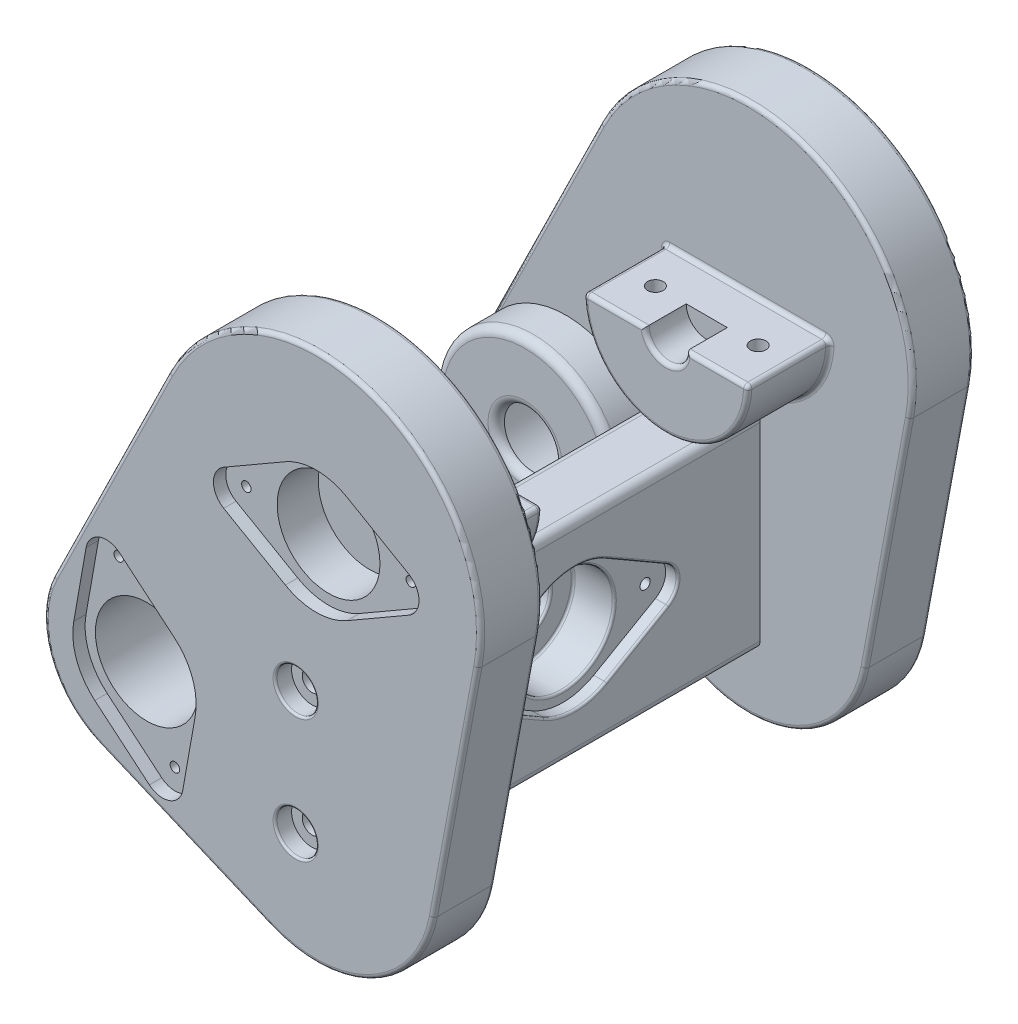
SolidWorks part; units mm, degrees
other "Markup1"
sketch "Sketch17" plane through (40, 40, -60) normal (0.6706, 0.1026, -0.7347) x (-0.7381, -0.0065, -0.6746)
ref_plane "Front Plane" through (0, 0, 0) normal (0, 0, 1) x (1, 0, 0)
ref_plane "Top Plane" through (0, 0, 0) normal (0, 1, 0) x (1, 0, 0)
ref_plane "Right Plane" through (0, 0, 0) normal (1, 0, 0) x (0, 0, -1)
ref_plane "Plane1" through (0, 0, 60) normal (0, 0, 1) x (1, 0, 0)
sketch "Sketch2" plane through (0, 0, 60) normal (0, 0, 1) x (1, 0, 0)
  line L2 (0, -60) -> (0, 0) construction
  line L3 (-39.322, -7.3333) -> (-28.5085, -65.3167)
  line L4 (39.322, -7.3333) -> (28.5085, -65.3167)
  circle A0 centre (0, 0) radius 30 construction
  arc A1 (39.322, -7.3333) -> (-39.322, -7.3333) centre (0, 0) ccw
  circle A2 centre (0, -60) radius 24 construction
  arc A3 (-28.5085, -65.3167) -> (28.5085, -65.3167) centre (0, -60) ccw
  circle A4 centre (0, 0) radius 12.5
  circle A5 centre (0, -60) radius 12.5 construction
  dimension "D1" = 60
  dimension "D2" = 10
  dimension "D5" = 48
  dimension "D6" = 5
  dimension "D7" = 25
  dimension "D8" = 25
  dimension "D3" = 60
extrude "Boss-Extrude1" add sketch "Sketch2" against normal blind 15
sketch "Sketch13" plane through (0, 0, 45) normal (0, 0, -1) x (-1, 0, 0)
  line L0 (0, 0) -> (0, -60) construction
  line L2 (13, -74) -> (-3, -74)
  line L3 (13, -74) -> (13, -24)
  line L4 (13, -24) -> (-3, -24)
  line L5 (-3, -74) -> (-3, -24)
  line L6 (13, -74) -> (-3, -24) construction
  line L7 (13, -24) -> (-3, -74) construction
  point P9 (5, -49)
  dimension "D1" = 16
  dimension "D2" = 50
  dimension "D3" = 11
  dimension "D4" = 5
extrude "Boss-Extrude5" add sketch "Sketch13" along normal up to surface (45 mm away) up to plane "Front Plane"
mirror "Mirror2" about plane through (0, 0, 0) normal (0, 0, 1) of "Boss-Extrude1", "Boss-Extrude5"
mirror "Mirror4" about plane through (0, 0, 0) normal (0, 0, 1) of "Boss-Extrude1"
sketch "Sketch5" plane through (0, 0, 0) normal (0, 0, 1) x (1, 0, 0)
  point P0 (0, 0)
sketch "Sketch14" plane through (3, 0, 0) normal (1, 0, 0) x (0, 0, -1)
  line L0 (45, -24) -> (-45, -24) construction
  circle A0 centre (0, -49) radius 12.5
  dimension "D1" = 25
  dimension "D2" = 25
extrude "Cut-Extrude1" cut sketch "Sketch14" against normal blind 13
sketch "Sketch15" plane through (3, 0, 0) normal (1, 0, 0) x (0, 0, -1)
  line L0 (-22.5, -44.6699) -> (-7.5, -36.0096)
  line L1 (7.5, -36.0096) -> (22.5, -44.6699)
  line L2 (-22.5, -53.3301) -> (-7.5, -61.9904)
  line L3 (7.5, -61.9904) -> (22.5, -53.3301)
  arc A0 (-7.5, -61.9904) -> (7.5, -61.9904) centre (0, -49) ccw
  circle A1 centre (20, -49) radius 1.25
  circle A2 centre (-20, -49) radius 1.25
  arc A3 (-22.5, -44.6699) -> (-22.5, -53.3301) centre (-20, -49) ccw
  arc A4 (22.5, -53.3301) -> (22.5, -44.6699) centre (20, -49) ccw
  arc A5 (7.5, -36.0096) -> (-7.5, -36.0096) centre (0, -49) ccw
  dimension "D1" = 30
  dimension "D2" = 2.5
  dimension "D3" = 20
  dimension "D4" = 20
extrude "Cut-Extrude2" cut sketch "Sketch15" against normal blind 3
sketch "Sketch16" plane through (3, 0, 0) normal (1, 0, 0) x (0, 0, -1)
  circle A0 centre (0, -49) radius 7
  circle A5 centre (20, -49) radius 1.25 construction
  circle A6 centre (-20, -49) radius 1.25 construction
  circle A7 centre (20, -49) radius 1.25
  circle A8 centre (-20, -49) radius 1.25
  dimension "D3" = 14
extrude "Cut-Extrude3" cut sketch "Sketch16" against normal through all
fillet "Fillet3" radius 0.5 3 edges at (-10, -49, -7) (0, -49, -12.5) (-10, -49, -12.5)
fillet "Fillet4" radius 0.5 1 edges at (-13, -49, -7)
fillet "Fillet5" radius 0.5 8 edges at (3, -34, 0) (3, -40.3397, -15) (3, -49, -25) (3, -57.6603, -15) (3, -64, 0) (3, -57.6603, 15) (3, -49, 25) (3, -40.3397, 15)
sketch "Sketch18" plane through (0, 0, 0) normal (0, 0, 1) x (1, 0, 0)
  line L0 (0, 0) -> (0, -49) construction
  line L1 (0, -49) -> (60, -49) construction
  line L2 (60, -49) -> (0, 0) construction
  dimension "D1" = 49
  dimension "D2" = 60
sketch "Sketch21" plane through (0, 0, 45) normal (0, 0, -1) x (-1, 0, 0)
  line L0 (0, 0) -> (0, -49) construction
  line L1 (0, -49) -> (-44.2154, -49) construction
  line L2 (-44.2154, -49) -> (0, 0) construction
  line L5 (-63.9491, -39.2748) -> (-35.8795, 17.6822)
  line L6 (-52.7436, -69.2798) -> (-11.2417, -86.7324)
  line L7 (-39.322, -7.3333) -> (-28.5085, -65.3167)
  line L8 (39.322, -7.3333) -> (32.1833, -45.612)
  line L9 (52.7436, -69.2798) -> (11.2417, -86.7324)
  line L10 (63.9491, -39.2748) -> (35.8795, 17.6822)
  line L11 (31.7709, -47.8233) -> (28.5085, -65.3167)
  line L12 (35.8795, 17.6822) -> (11.2417, -86.7324)
  circle A0 centre (0, 0) radius 44 construction
  arc A1 (-63.9491, -39.2748) -> (-52.7436, -69.2798) centre (-44.2154, -49) ccw
  arc A2 (-28.5085, -65.3167) -> (28.5085, -65.3167) centre (0, -60) ccw construction
  arc A3 (39.322, -7.3333) -> (-39.322, -7.3333) centre (0, 0) ccw construction
  arc A4 (-11.2417, -86.7324) -> (28.5085, -65.3167) centre (0, -60) ccw
  arc A5 (39.322, -7.3333) -> (-35.8795, 17.6822) centre (0, 0) ccw
  arc A6 (-35.8795, 17.6822) -> (-39.322, -7.3333) centre (0, 0) ccw
  arc A7 (-11.2417, -86.7324) -> (-28.5085, -65.3167) centre (0, -60) cw
  circle A8 centre (-44.2154, -49) radius 12.5
  arc A9 (11.2417, -86.7324) -> (28.5085, -65.3167) centre (0, -60) ccw
  arc A10 (35.8795, 17.6822) -> (39.322, -7.3333) centre (0, 0) cw
  arc A11 (63.9491, -39.2748) -> (52.7436, -69.2798) centre (44.2154, -49) cw
  circle A12 centre (44.2154, -49) radius 12.5
  arc M4 (39.322, -7.3333) -> (-39.322, -7.3333) centre (0, 0) ccw
  arc M6 (-28.5085, -65.3167) -> (28.5085, -65.3167) centre (0, -60) ccw
  line M7 (28.5085, -65.3167) -> (39.322, -7.3333)
  dimension "D2" = 88
  dimension "D3" = 44
  dimension "D4" = 25
  dimension "D1" = 66
extrude "Boss-Extrude7" add sketch "Sketch21" against normal blind 15 contours A12 L9 A11 L10 M7 M6 M4 | A12 L12 M7 M4 M6
sketch "Sketch23" plane through (0, 0, 45) normal (0, 0, -1) x (-1, 0, 0)
  arc A1 (52.7436, -69.2798) -> (63.9491, -39.2748) centre (44.2154, -49) ccw construction
  circle A4 centre (44.2154, -49) radius 12.5
  circle A5 centre (44.2154, -49) radius 22
  dimension "D2" = 25
extrude "Boss-Extrude8" add sketch "Sketch23" along normal blind 10
sketch "Sketch24" plane through (0, 0, 35) normal (0, 0, -1) x (-1, 0, 0)
  circle A0 centre (44.2154, -49) radius 12.5
extrude "Cut-Extrude4" cut sketch "Sketch24" against normal through all
sketch "Sketch25" plane through (0, 0, 35) normal (0, 0, -1) x (-1, 0, 0)
  circle A0 centre (44.2154, -49) radius 12.5
  circle A1 centre (44.2154, -49) radius 7
  dimension "D1" = 14
  dimension "D2" = 25
extrude "Boss-Extrude9" add sketch "Sketch25" against normal blind 2
sketch "Sketch26" plane through (0, 0, 60) normal (0, 0, 1) x (1, 0, 0)
  line L0 (-51.0558, -30.2061) -> (-37.375, -67.7939) construction
  line L1 (-44.2154, -49) -> (-29.2154, -49) construction
  line L2 (-34.5736, -37.5093) -> (-47.8418, -26.3759)
  line L3 (-55.9798, -29.3379) -> (-58.9875, -46.3953)
  line L4 (-29.4433, -51.6047) -> (-32.4509, -68.6621)
  line L5 (-53.8572, -60.4907) -> (-40.5889, -71.6241)
  arc A0 (-58.9875, -46.3953) -> (-53.8572, -60.4907) centre (-44.2154, -49) ccw
  arc A1 (-40.5889, -71.6241) -> (-32.4509, -68.6621) centre (-37.375, -67.7939) ccw
  arc A2 (-47.8418, -26.3759) -> (-55.9798, -29.3379) centre (-51.0558, -30.2061) ccw
  arc A3 (-29.4433, -51.6047) -> (-34.5736, -37.5093) centre (-44.2154, -49) ccw
  point P5 (-44.2154, -49)
  dimension "D1" = 30
  dimension "D2" = 40
  dimension "D3" = 110
extrude "Cut-Extrude5" cut sketch "Sketch26" against normal blind 3
sketch "Sketch27" plane through (0, 0, 57) normal (0, 0, 1) x (1, 0, 0)
  circle A0 centre (-51.0558, -30.2061) radius 1.15
  circle A1 centre (-37.375, -67.7939) radius 1.15
  dimension "D1" = 2.3
  dimension "D2" = 2.3
extrude "Cut-Extrude6" cut sketch "Sketch27" against normal blind 8
mirror "Mirror12" about plane through (0, 0, 0) normal (0, 0, 1) of "Cut-Extrude6", "Boss-Extrude9", "Cut-Extrude5", "Cut-Extrude4", "Boss-Extrude8", "Boss-Extrude7"
sketch "Sketch28" plane through (0, 0, 45) normal (0, 0, -1) x (-1, 0, 0)
  circle A0 centre (0, 0) radius 20
  dimension "D1" = 40
extrude "Boss-Extrude10" add sketch "Sketch28" against normal blind 2
sketch "Sketch29" plane through (0, 0, 45) normal (0, 0, -1) x (-1, 0, 0)
  line L0 (-20, 0) -> (20, 0)
  arc A0 (-20, 0) -> (20, 0) centre (0, 0) ccw
  dimension "D1" = 40
extrude "Boss-Extrude11" add sketch "Sketch29" along normal blind 20
sketch "Sketch30" plane through (0, 0, 25) normal (0, 0, -1) x (-1, 0, 0)
  line L0 (20, 0) -> (-20, 0) construction
  circle A0 centre (0, 0) radius 5
  dimension "D1" = 10
extrude "Cut-Extrude7" cut sketch "Sketch30" against normal blind 10
sketch "Sketch31" plane through (0, 0, 0) normal (0, 1, 0) x (1, 0, 0)
  line L0 (-20, -25) -> (-5, -25) construction
  line L1 (-12.5, -25) -> (12.5, -25)
  line L2 (-12.5, -25) -> (-12.5, -35) construction
  line L3 (-12.5, -35) -> (12.5, -35) construction
  line L4 (12.5, -25) -> (12.5, -35) construction
  line L6 (5, -25) -> (20, -25) construction
  line L8 (5, -35) -> (-5, -35) construction
  circle A0 centre (12.5, -35) radius 1.9
  circle A1 centre (-12.5, -35) radius 1.9
  point P8 (12.5, -25)
  dimension "D2" = 3.8
  dimension "D3" = 3.8
extrude "Cut-Extrude8" cut sketch "Sketch31" against normal blind 12 contours A1 | A0
sketch "Sketch32" plane through (-30.9224, 58.3079, 60) normal (0, 0, 1) x (0.342, 0.9397, 0)
  line L0 (-51.0558, -30.2061) -> (-37.375, -67.7939) construction
  line L1 (-44.2154, -49) -> (-29.2154, -49) construction
  line L2 (-34.5736, -37.5093) -> (-47.8418, -26.3759)
  line L3 (-55.9798, -29.3379) -> (-58.9875, -46.3953)
  line L4 (-29.4433, -51.6047) -> (-32.4509, -68.6621)
  line L5 (-53.8572, -60.4907) -> (-40.5889, -71.6241)
  line L6 (-90.2603, -65.759) -> (-69.7391, -122.1405) construction
  arc A0 (-58.9875, -46.3953) -> (-53.8572, -60.4907) centre (-44.2154, -49) ccw
  arc A1 (-40.5889, -71.6241) -> (-32.4509, -68.6621) centre (-37.375, -67.7939) ccw
  arc A2 (-47.8418, -26.3759) -> (-55.9798, -29.3379) centre (-51.0558, -30.2061) ccw
  arc A3 (-29.4433, -51.6047) -> (-34.5736, -37.5093) centre (-44.2154, -49) ccw
  circle A4 centre (-44.2154, -49) radius 12.5 construction
extrude "Cut-Extrude9" cut sketch "Sketch32" against normal blind 3
sketch "Sketch33" plane through (0, 0, 57) normal (0, 0, 1) x (1, 0, 0)
  circle A0 centre (20, 0) radius 1.15
  circle A1 centre (-20, 0) radius 1.15
  dimension "D1" = 2.3
extrude "Cut-Extrude10" cut sketch "Sketch33" against normal blind 8
mirror "Mirror13" about plane through (0, 0, 0) normal (0, 0, 1) of "Boss-Extrude11", "Cut-Extrude7", "Cut-Extrude8", "Cut-Extrude9", "Cut-Extrude10", "Boss-Extrude10"
fillet "Fillet6" radius 1 22 edges at (-31.9927, -78.0061, -45) (-31.9927, -78.0061, -60) (13.7548, -85.5305, -45) (-49.9143, -10.7963, -45) (-49.9143, -10.7963, -60) (12.6256, 37.9551, -45) (13.7548, -85.5305, -60) (-64.8251, -56.6968, -60) (12.6256, 37.9551, -60) (-31.9927, -78.0061, 45) (-31.9927, -78.0061, 60) (13.7548, -85.5305, 45) (-49.9143, -10.7963, 45) (-49.9143, -10.7963, 60) (12.6256, 37.9551, 45) (13.7548, -85.5305, 60) (-64.8251, -56.6968, 60) (12.6256, 37.9551, 60) (33.9153, -36.325, -45) (33.9153, -36.325, -60) (33.9153, -36.325, 45) (33.9153, -36.325, 60)
fillet "Fillet7" radius 1 16 edges at (20, 0, -35) (0, 0, -45) (-20, 0, -35) (0, 0, 45) (0, -20, -25) (0, -20, -45) (-20, 0, 35) (20, 0, 35) (0, -20, 25) (0, -20, 45) (0, -5, -25) (0, -5, 25) (12.5, 0, 25) (-12.5, 0, 25) (-12.5, 0, -25) (12.5, 0, -25)
fillet "Fillet8" radius 2 4 edges at (-13, -74, 0) (3, -74, 0) (-13, -24, 0) (3, -24, 0)
fillet "Fillet9" radius 2 4 edges at (-51.2154, -49, -35) (-66.2154, -49, -35) (-51.2154, -49, 35) (-66.2154, -49, 35)
sketch "Sketch35" plane through (0, 0, 60) normal (0, 0, 1) x (1, 0, 0)
  line L0 (-5, -49) -> (-5, -34) construction
  line L1 (-5, -49) -> (-5, -64) construction
  line L2 (-13, -24) -> (3, -74) construction
  line L3 (-13, -74) -> (3, -24) construction
  line L4 (-13, -74) -> (3, -74) construction
  line L5 (-13, -74) -> (-13, -24) construction
  line L6 (-13, -24) -> (3, -24) construction
  line L7 (3, -74) -> (3, -24) construction
  line L8 (-13, -24) -> (3, -74) construction
  line L9 (-13, -74) -> (3, -24) construction
  line L10 (-13, -74) -> (3, -74) construction
  line L11 (-13, -74) -> (-13, -24) construction
  line L12 (-13, -24) -> (3, -24) construction
  line L13 (3, -74) -> (3, -24) construction
  circle A0 centre (-5, -34) radius 2.4
  circle A1 centre (-5, -64) radius 2.4
  dimension "D2" = 4.8
  dimension "D3" = 4.8
  dimension "D1" = 10
extrude "Cut-Extrude12" cut sketch "Sketch35" against normal through all
sketch "Sketch37" plane through (0, 0, 60) normal (0, 0, 1) x (1, 0, 0)
  circle A0 centre (-5, -34) radius 5
  circle A1 centre (-5, -64) radius 5
  dimension "D1" = 10
extrude "Cut-Extrude14" cut sketch "Sketch37" against normal blind 4
fillet "Fillet11" radius 0.5 2 edges at (0, -64, 60) (0, -34, 60)
